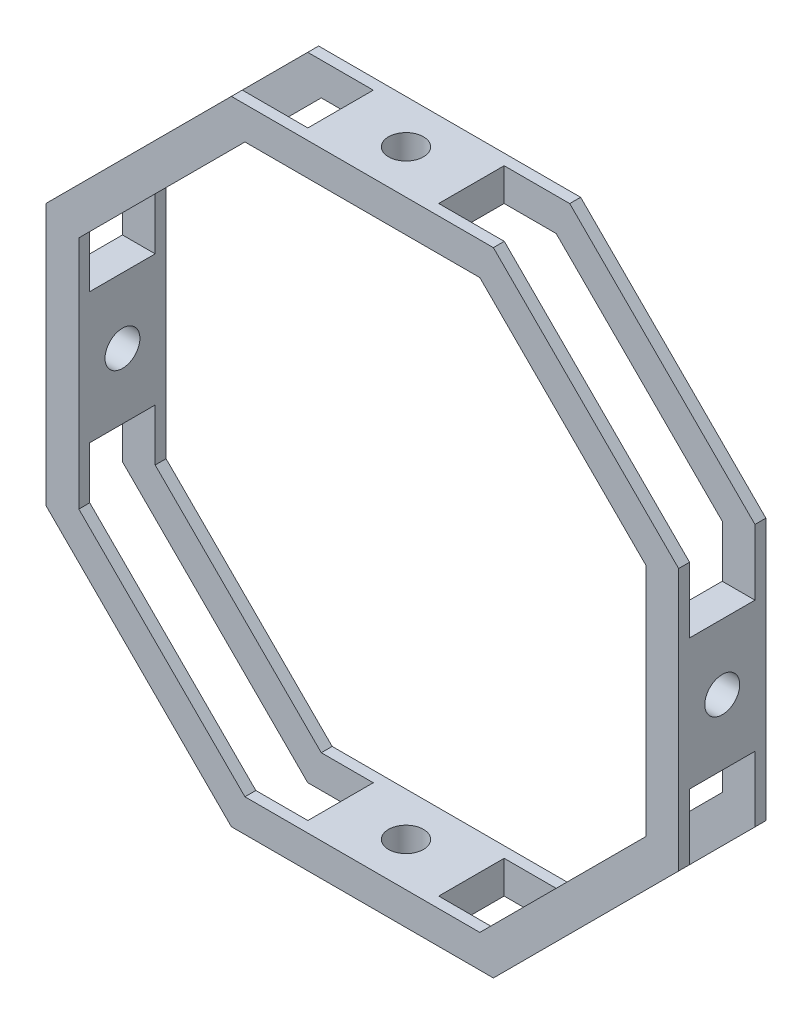
SolidWorks part; units mm, degrees
ref_plane "Plano frontal" through (0, 0, 0) normal (0, 0, 1) x (1, 0, 0)
ref_plane "Plano superior" through (0, 0, 0) normal (0, 1, 0) x (1, 0, 0)
ref_plane "Plano direito" through (0, 0, 0) normal (1, 0, 0) x (0, 0, -1)
sketch "Esboço1" plane through (0, 0, 0) normal (0, 0, 1) x (1, 0, 0)
  line L1 (145, 60.061) -> (60.061, 145)
  line L2 (60.061, 145) -> (-60.061, 145)
  line L3 (-60.061, 145) -> (-145, 60.061)
  line L4 (-145, 60.061) -> (-145, -60.061)
  line L5 (-145, -60.061) -> (-60.061, -145)
  line L6 (-60.061, -145) -> (60.061, -145)
  line L7 (60.061, -145) -> (145, -60.061)
  line L8 (145, -60.061) -> (145, 60.061)
  line L9 (130, 53.8478) -> (53.8478, 130)
  line L10 (53.8478, 130) -> (-53.8478, 130)
  line L11 (-53.8478, 130) -> (-130, 53.8478)
  line L12 (-130, 53.8478) -> (-130, -53.8478)
  line L13 (-130, -53.8478) -> (-53.8478, -130)
  line L14 (-53.8478, -130) -> (53.8478, -130)
  line L15 (53.8478, -130) -> (130, -53.8478)
  line L16 (130, -53.8478) -> (130, 53.8478)
  circle A0 centre (0, 0) radius 145 construction
  circle A1 centre (0, 0) radius 130 construction
extrude "Ressalto-extrusão1" add sketch "Esboço1" along normal blind 40
sketch "Esboço2" plane through (145, 0, 0) normal (1, 0, 0) x (0, 0, -1)
  line L0 (-40, -60.061) -> (-40, 60.061) construction
  line L1 (0, 0) -> (-40, 0)
  line L2 (0, 0) -> (0, 30)
  line L3 (0, 30) -> (-40, 30)
  line L4 (-40, 0) -> (-40, 30)
  line L5 (-40, -60.061) -> (0, -60.061) construction
  line L6 (0, 0) -> (-40, 0)
  line L7 (0, 0) -> (0, -30)
  line L8 (0, -30) -> (-40, -30)
  line L9 (-40, 0) -> (-40, -30)
  line L10 (0, 60.061) -> (-5, 60.061)
  line L11 (0, 60.061) -> (0, 30)
  line L12 (0, 30) -> (-5, 30)
  line L13 (-5, 60.061) -> (-5, 30)
  line L14 (-40, 60.061) -> (-35, 60.061)
  line L15 (-40, 60.061) -> (-40, 30)
  line L16 (-40, 30) -> (-35, 30)
  line L17 (-35, 60.061) -> (-35, 30)
  line L18 (-35, -30) -> (-5, -30)
  line L19 (-35, -30) -> (-35, -60.061)
  line L20 (-35, -60.061) -> (-5, -60.061)
  line L21 (-5, -30) -> (-5, -60.061)
  circle A0 centre (-20, 0) radius 8
  line M2 (0, 60.061) -> (-40, 60.061)
  line M4 (-40, -60.061) -> (0, -60.061)
extrude "Corte-extrusão1" cut sketch "Esboço2" against normal through all both and the other way through all contours L17 L3 L13 M2 | L21 L8 L19 M4 | A0 region at (145, 45.0305, 20) region at (145, -45.0305, 20)
sketch "Esboço3" plane through (102.5305, 102.5305, 0) normal (0.7071, 0.7071, 0) x (0, 0, -1)
  line L0 (-40, 60.061) -> (0, 60.061) construction
  line L1 (-35, -60.061) -> (-5, -60.061)
  line L2 (-35, -60.061) -> (-35, 60.061)
  line L3 (-35, 60.061) -> (-5, 60.061)
  line L4 (-5, -60.061) -> (-5, 60.061)
extrude "Corte-extrusão2" cut sketch "Esboço3" against normal through all both and the other way through all
sketch "Esboço4" plane through (0, 145, 0) normal (0, 1, 0) x (1, 0, 0)
  line L0 (60.061, -40) -> (-60.061, -40) construction
  line L1 (0, 0) -> (30, 0)
  line L2 (0, 0) -> (0, -40)
  line L3 (0, -40) -> (30, -40)
  line L4 (30, 0) -> (30, -40)
  line L5 (-60.061, -40) -> (-60.061, 0) construction
  line L6 (0, 0) -> (-30, 0)
  line L7 (0, 0) -> (0, -40)
  line L8 (0, -40) -> (-30, -40)
  line L9 (-30, 0) -> (-30, -40)
  line L10 (60.061, 0) -> (30, 0)
  line L11 (60.061, 0) -> (60.061, -5)
  line L12 (60.061, -5) -> (30, -5)
  line L13 (30, 0) -> (30, -5)
  line L14 (60.061, -35) -> (30, -35)
  line L15 (60.061, -35) -> (60.061, -40)
  line L16 (60.061, -40) -> (30, -40)
  line L17 (30, -35) -> (30, -40)
  line L18 (-30, -5) -> (-60.061, -5)
  line L19 (-30, -5) -> (-30, -35)
  line L20 (-30, -35) -> (-60.061, -35)
  line L21 (-60.061, -5) -> (-60.061, -35)
  line M2 (-60.061, 0) -> (-60.061, -40)
  line M5 (60.061, -35) -> (60.061, -5)
sketch "Esboço5" plane through (0, 145, 0) normal (0, 1, 0) x (1, 0, 0)
  line L0 (0, 0) -> (0, -40) construction
  circle A0 centre (0, -20) radius 8
extrude "Corte-extrusão3" cut sketch "Esboço5" against normal through all both and the other way through all contours A0
extrude "Corte-extrusão4" cut sketch "Esboço4" against normal through all both and the other way through all contours L14 L12 L4 M5 | L20 L9 L18 M2 region at (45.0305, 145, 20) region at (-45.0305, 145, 20)
sketch "Esboço7" plane through (-102.5305, 102.5305, 0) normal (-0.7071, 0.7071, 0) x (0, 0, 1)
  line L0 (35, 60.061) -> (5, 60.061) construction
  line L1 (5, -60.061) -> (35, -60.061)
  line L2 (5, -60.061) -> (5, 60.061)
  line L3 (5, 60.061) -> (35, 60.061)
  line L4 (35, -60.061) -> (35, 60.061)
  line L5 (35, 60.061) -> (35, 81.3173) construction
extrude "Corte-extrusão5" cut sketch "Esboço7" against normal through all both and the other way through all
